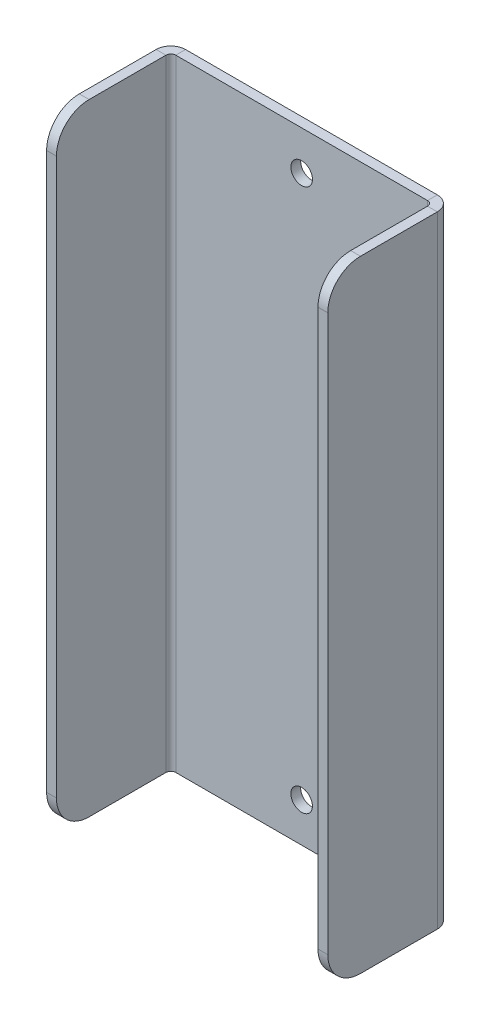
SolidWorks part; units mm, degrees
note: The reader was unsure of these and kept them because the rebuilt part matched: flange length of "Brida de arista1".
ref_plane "Alzado" through (0, 0, 0) normal (0, 0, 1) x (1, 0, 0)
ref_plane "Planta" through (0, 0, 0) normal (0, 1, 0) x (1, 0, 0)
ref_plane "Vista lateral" through (0, 0, 0) normal (1, 0, 0) x (0, 0, -1)
sketch "Croquis1" plane through (0, 0, 0) normal (0, 0, 1) x (1, 0, 0)
  line L0 (40, 0) -> (-40, 0) construction
  line L2 (-40, 95) -> (40, 95)
  line L3 (-40, 95) -> (-40, -95)
  line L4 (-40, -95) -> (40, -95)
  line L5 (40, 95) -> (40, -95)
  dimension "D1" = 80
  dimension "D2" = 190
sheet metal parameters "Chapa metálica1" thickness 3 parameters "D1"=1.5
base flange "Brida base1" sketch "Croquis1" thickness 3 reverse thickness direction no parameters "D1"=1.5
edge flange "Brida de arista1" sketch "Croquis8" flange profiles "Croquis8", "Croquis9" flange angle 90 flange length 35 flange position material outside bend radius 1.5 thickness 3 relief rectangular parameters "D6"=10, "D8"=1
sketch "Croquis8" plane through (-40, 0, 0) normal (-1, 0, 0) x (0, -1, 0)
  line L0 (-95, 0) -> (95, 0) construction
  line L1 (-95, 0) -> (95, 0)
  line L2 (-95, 0) -> (-95, 35)
  line L3 (-95, 35) -> (95, 35)
  line L4 (95, 35) -> (95, 0)
sketch "Croquis9" plane through (40, 0, 0) normal (1, 0, 0) x (0, 1, 0)
  line L0 (-95, 0) -> (95, 0) construction
  line L1 (-95, 0) -> (95, 0)
  line L2 (-95, 0) -> (-95, 35)
  line L3 (-95, 35) -> (95, 35)
  line L4 (95, 35) -> (95, 0)
bend "Pliegue de arista1" bend radius 1.5 bend angle 90 parameters "D5"=1
bend "Pliegue de arista2" bend radius 1.5 bend angle 90 parameters "D5"=2
fillet "Redondeo1" [suppressed] radius 20
hole_wizard "Taladro de margen para M61" positions "Croquis11" profile "Croquis10" hole size "M6" standard "Ansi Metric"
sketch "Croquis11" plane through (0, 0, 0) normal (0, 0, 1) x (1, 0, 0)
  line L0 (0, 95) -> (0, -95) construction
  line L1 (38.5, 95) -> (-38.5, 95) construction
  line L2 (-38.5, -95) -> (38.5, -95) construction
  point P9 (0, 83)
  point P11 (0, -83)
  dimension "D1" = 166
  dimension "D2" = 83
sketch "Croquis10" plane through (0, 83, 0) normal (1, 0, 0) x (0, -1, 0)
  line L0 (0, 0) -> (0, 501.9828)
  line L1 (0, 501.9828) -> (3.3, 500)
  line L2 (3.3, 500) -> (3.3, 0)
  line L5 (3.3, 0) -> (0, 0)
  line L10 (0, 501.9828) -> (-3.3, 500) construction
  line L11 (0, -6.35) -> (0, 107.95) construction
  dimension "Diámetro de taladro" = 6.6
  dimension "Profundidad de taladro" = 500
  dimension "Ángulo de perforador" = 118
fillet "Redondeo2" radius 10 4 edges at (-41.5, -95, 35) (41.5, -95, 35) (-41.5, 95, 35) (41.5, 95, 35)
flat pattern "Chapa desplegada1" [suppressed]
sketch "Líneas de pliegue1" plane through (0, 0, 0) normal (0, 0, 1) x (1, 0, 0)
  line L0 (40.3284, -95) -> (40.3284, 95) construction
  line L1 (-40.3284, 95) -> (-40.3284, -95) construction
  line L2 (40.3284, -95) -> (40.3284, 95) construction
  line L3 (-40.3284, 95) -> (-40.3284, -95) construction
sketch3d "Cuadro delimitador1" [suppressed]
  line L0 (75.6568, 95, 0) -> (75.6568, -95, 0) construction
  line L1 (-75.6568, 95, 0) -> (-75.6568, -95, 0) construction
  line L2 (75.6568, 95, 0) -> (-75.6568, 95, 0) construction
  line L3 (75.6568, -95, 0) -> (-75.6568, -95, 0) construction
bend of the flat pattern "Aplanar-<Pliegue de arista1>1"
bend of the flat pattern "Aplanar-<Pliegue de arista2>1"
